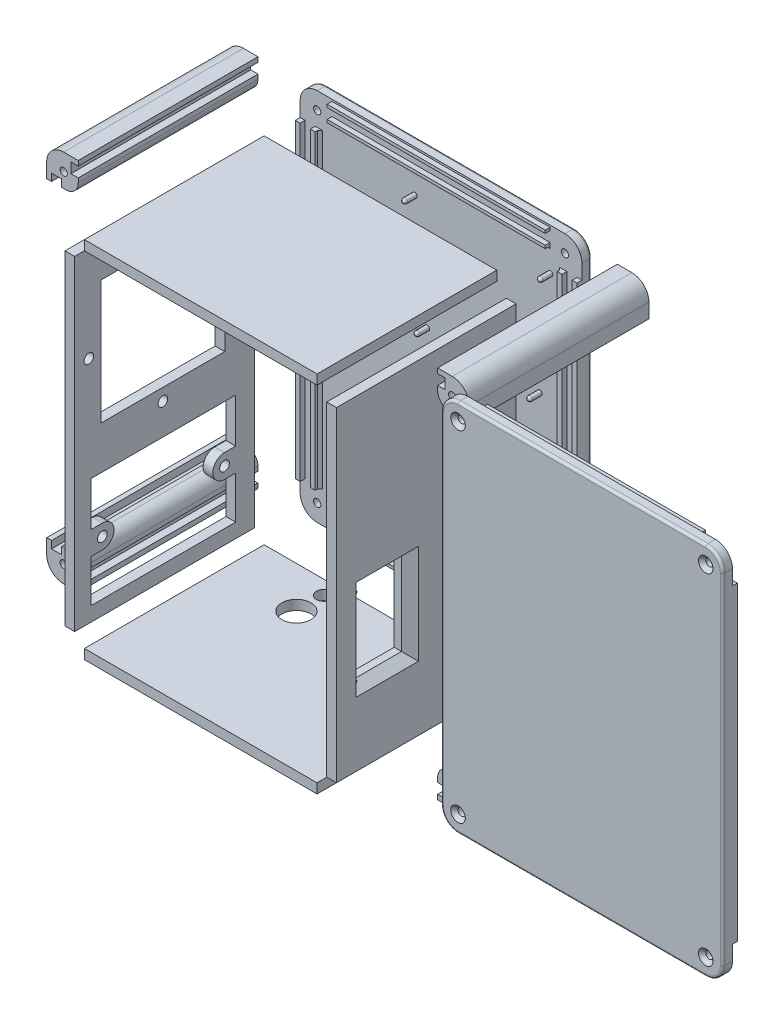
SolidWorks part; units mm, degrees
note: The reader was unsure of these and kept them because the rebuilt part matched: shared geometry of "Эскиз10<3>", "Эскиз10<4>".
other "Розетка"
other "Стойка 4"
other "Стойка 3"
other "Стойка 2"
other "Стойка 1"
other "Левая стенка"
other "Правая стенка"
other "НК"
other "ВК"
ref_plane "Спереди" through (0, 0, 0) normal (0, 0, 1) x (1, 0, 0)
ref_plane "Сверху" through (0, 0, 0) normal (0, 1, 0) x (1, 0, 0)
ref_plane "Справа" through (0, 0, 0) normal (1, 0, 0) x (0, 0, -1)
sketch "Эскиз1" plane through (0, 0, 0) normal (0, 0, 1) x (1, 0, 0)
  line L0 (-59.9, -15.0083) -> (-59.9, -81.9083)
  line L1 (-55.9, 51.8917) -> (-55.9, -81.9083)
  line L2 (-59.9, -81.9083) -> (-55.9, -81.9083)
  line L3 (-60, -82.0083) -> (-60, -79.0083)
  line L4 (-59.9, -15.0083) -> (-59.9, -82.0083) construction
  line L5 (-59.9, 51.8917) -> (-59.9, -81.9083)
  line L7 (-59.9, -15.0083) -> (-59.9, -81.9083)
  line L8 (-55.9, 51.8917) -> (-55.9, -81.9083)
  line L9 (-59.9, -81.9083) -> (-55.9, -81.9083)
  line L10 (-59.9, 51.8917) -> (-59.9, -81.9083)
  line L11 (-55.9, 51.8917) -> (-55.9, -81.9083)
  line L12 (43.9, -85.9083) -> (-51.9, -85.9083)
  line L13 (44, -87.9083) -> (-52, -87.9083) construction
  line L14 (-4, 59.9917) -> (-4, -91.0083) construction
  line L15 (-55, 61.9917) -> (-49, 61.9917)
  line L16 (-54, -79.0083) -> (-55.8, -79.0083)
  line L17 (-61, -79.0083) -> (-62, -79.0083)
  line L18 (-51.9, -89.9083) -> (-51.9, -85.9083)
  line L22 (-55.8, -82.0083) -> (-60, -82.0083)
  line L23 (-55.8, -82.0083) -> (-55.8, -79.0083)
  line L24 (-60, -90.0083) -> (-49, -79.0083) construction
  line L25 (-60, -79.0083) -> (-61, -79.0083)
  line L26 (54, 54.9917) -> (54, 48.9917)
  line L27 (47, 61.9917) -> (41, 61.9917)
  line L28 (48.0607, 56.0524) -> (41, 48.9917) construction
  line L29 (43.9, -89.9083) -> (-51.9, -89.9083)
  line L31 (-49, -90.0083) -> (-49, -92.0083)
  line L32 (-52, -85.8083) -> (-49, -85.8083)
  line L33 (-52, -85.8083) -> (-52, -90.0083)
  line L35 (-49, -84.0083) -> (-49, -85.8083)
  line L36 (-52, -90.0083) -> (-49, -90.0083)
  line L37 (-57.9, -81.9083) -> (-57.9, -82.0083) construction
  line L38 (49.9, 51.9917) -> (49.9, 51.8917) construction
  line L42 (52, -90.0083) -> (41, -79.0083) construction
  line L43 (44, -90.0083) -> (41, -90.0083)
  line L44 (41, -84.0083) -> (41, -85.8083)
  line L46 (44, -85.8083) -> (44, -90.0083)
  line L47 (44, -85.8083) -> (41, -85.8083)
  line L48 (41, -90.0083) -> (41, -92.0083)
  line L49 (52, -79.0083) -> (54, -79.0083)
  line L50 (47.8, -82.0083) -> (47.8, -79.0083)
  line L51 (47.8, -82.0083) -> (52, -82.0083)
  line L53 (43.9, -89.9083) -> (43.9, -85.9083)
  line L54 (46, -79.0083) -> (47.8, -79.0083)
  line L55 (47.9, 51.8917) -> (47.9, -81.9083)
  line L56 (51.9, 51.8917) -> (51.9, -81.9083)
  line L57 (51.9, -81.9083) -> (47.9, -81.9083)
  line L58 (47.9, 51.8917) -> (47.9, -81.9083)
  line L59 (51.9, 51.8917) -> (51.9, -81.9083)
  line L60 (51.9, 51.8917) -> (51.9, -81.9083)
  line L61 (52, -82.0083) -> (52, -79.0083)
  line L62 (51.9, -81.9083) -> (47.9, -81.9083)
  line L63 (47.9, 51.8917) -> (47.9, -81.9083)
  line L64 (51.9, 51.8917) -> (51.9, -81.9083)
  line L65 (52, 59.9917) -> (50.5355, 58.5272) construction
  line L66 (-57.9, 51.8917) -> (-57.9, 51.9917) construction
  line L67 (-60, 59.9917) -> (-49, 48.9917) construction
  line L68 (44, 57.8917) -> (-52, 57.8917) construction
  line L69 (51.9, 51.8917) -> (47.9, 51.8917)
  line L70 (52, 51.9917) -> (52, 48.9917)
  line L71 (51.9, 51.8917) -> (47.9, 51.8917)
  line L72 (46, 48.9917) -> (47.8, 48.9917)
  line L73 (43.9, 59.8917) -> (43.9, 55.8917)
  line L75 (47.8, 51.9917) -> (52, 51.9917)
  line L76 (47.8, 51.9917) -> (47.8, 48.9917)
  line L77 (52, 48.9917) -> (54, 48.9917)
  line L78 (41, 59.9917) -> (41, 61.9917)
  line L79 (44, 55.7917) -> (41, 55.7917)
  line L80 (44, 55.7917) -> (44, 59.9917)
  line L82 (41, 53.9917) -> (41, 55.7917)
  line L83 (44, 59.9917) -> (41, 59.9917)
  line L84 (-52, 59.9917) -> (-49, 59.9917)
  line L85 (-49, 53.9917) -> (-49, 55.7917)
  line L87 (-52, 55.7917) -> (-52, 59.9917)
  line L88 (-52, 55.7917) -> (-49, 55.7917)
  line L89 (-49, 59.9917) -> (-49, 61.9917)
  line L90 (43.9, 59.8917) -> (-51.9, 59.8917)
  line L91 (-60, 48.9917) -> (-62, 48.9917)
  line L92 (-55.8, 51.9917) -> (-55.8, 48.9917)
  line L93 (-55.8, 51.9917) -> (-60, 51.9917)
  line L95 (-51.9, 59.8917) -> (-51.9, 55.8917)
  line L96 (-54, 48.9917) -> (-55.8, 48.9917)
  line L97 (43.9, 55.8917) -> (-51.9, 55.8917)
  line L98 (-59.9, 51.8917) -> (-55.9, 51.8917)
  line L99 (-59.9, -15.0083) -> (-59.9, 51.8917)
  line L100 (-60, 51.9917) -> (-60, 48.9917)
  line L101 (-59.9, 51.8917) -> (-55.9, 51.8917)
  line L102 (-59.9, -15.0083) -> (-59.9, 51.8917)
  line L103 (49.9, -81.9083) -> (49.9, -82.0083) construction
  line L104 (-55.9, -15.0083) -> (47.9, -15.0083) construction
  line L105 (-57.9, -15.0083) -> (-57.9, -82.0083) construction
  line L106 (-62, 54.9917) -> (-62, 48.9917)
  line L107 (44, 59.9917) -> (41, 59.9917)
  line L108 (52, 51.9917) -> (52, 48.9917)
  line L109 (47, -92.0083) -> (41, -92.0083)
  line L110 (54, -85.0083) -> (54, -79.0083)
  line L111 (-62, -85.0083) -> (-62, -79.0083)
  line L112 (-55, -92.0083) -> (-49, -92.0083)
  circle A0 centre (47, -85.0083) radius 1.5
  arc A1 (41, -84.0083) -> (46, -79.0083) centre (46, -84.0083) cw
  circle A3 centre (-55, 54.9917) radius 1.5
  arc A4 (-49, 53.9917) -> (-54, 48.9917) centre (-54, 53.9917) cw
  arc A8 (41, 53.9917) -> (46, 48.9917) centre (46, 53.9917) ccw
  circle A9 centre (47, 54.9917) radius 1.5
  arc A10 (-62, 54.9917) -> (-55, 61.9917) centre (-55, 54.9917) cw
  arc A11 (-49, -84.0083) -> (-54, -79.0083) centre (-54, -84.0083) ccw
  circle A16 centre (-55, -85.0083) radius 1.5
  arc A17 (54, 54.9917) -> (47, 61.9917) centre (47, 54.9917) ccw
  arc A25 (54, -85.0083) -> (47, -92.0083) centre (47, -85.0083) cw
  arc A26 (-62, -85.0083) -> (-55, -92.0083) centre (-55, -85.0083) ccw
  point P3 (-60, 59.9917)
  point P4 (52, 59.9917)
  point P5 (-60, -90.0083)
  point P19 (52, 59.9917)
  point P40 (-4, -87.9083)
  point P82 (-4, -89.9083)
  point P88 (-4, -85.9083)
  point P90 (47.9, -15.0083)
  point P92 (52, -90.0083)
  point P96 (49.9, -15.0083)
  point P119 (51.9, -15.0083)
  point P143 (-55.9, -15.0083)
  point P144 (-4, 55.8917)
  point P145 (-4, 59.8917)
  point P146 (-4, 57.8917)
  point P147 (-60, 59.9917)
  dimension "D3" = 3
  dimension "D2" = 4.2
  dimension "D4" = 2
  dimension "D6" = 0.1
extrude "Бобышка-Вытянуть1" add sketch "Эскиз1" along normal blind 74
ref_plane "Плоскость5" through (0, 0, -0.1) normal (0, 0, -1) x (-1, 0, 0)
sketch "Эскиз3" plane through (0, 0, -0.1) normal (0, 0, -1) x (-1, 0, 0)
  line L13 (4, 60.9917) -> (4, -91.0083) construction
  line L14 (-53, -15.0083) -> (61, -15.0083) construction
  line L15 (-41, 61.9917) -> (-47, 61.9917)
  line L16 (-54, 54.9917) -> (-54, 48.9917)
  line L17 (-54, 48.9917) -> (-54, -79.0083)
  line L18 (-54, -79.0083) -> (-54, -85.0083)
  line L19 (-47, -92.0083) -> (-41, -92.0083)
  line L20 (-41, -92.0083) -> (49, -92.0083)
  line L21 (49, -92.0083) -> (55, -92.0083)
  line L22 (62, -85.0083) -> (62, -79.0083)
  line L23 (62, -79.0083) -> (62, 48.9917)
  line L24 (62, 48.9917) -> (62, 54.9917)
  line L25 (55, 61.9917) -> (49, 61.9917)
  line L26 (49, 61.9917) -> (-41, 61.9917)
  arc A5 (-47, 61.9917) -> (-54, 54.9917) centre (-47, 54.9917) ccw
  arc A6 (-54, -85.0083) -> (-47, -92.0083) centre (-47, -85.0083) ccw
  arc A7 (55, -92.0083) -> (62, -85.0083) centre (55, -85.0083) ccw construction
  arc A8 (55, -92.0083) -> (62, -85.0083) centre (55, -85.0083) ccw
  arc A9 (62, 54.9917) -> (55, 61.9917) centre (55, 54.9917) ccw construction
  arc A10 (62, 54.9917) -> (55, 61.9917) centre (55, 54.9917) ccw
  point P41 (-47, 54.9917)
extrude "Бобышка-Вытянуть3" add sketch "Эскиз3" along normal blind 4 separate body
sketch "Эскиз4" plane through (0, 0, -0.1) normal (0, 0, 1) x (1, 0, 0)
  line L0 (-4, 61.2063) -> (-4, -91.0083) construction
  line L2 (-62, -85.0083) -> (-62, 54.9917) construction
  line L3 (-62, -15.0083) -> (54, -15.0083) construction
  line L6 (-60, 48.8917) -> (-60, -78.9083)
  line L7 (-62, 48.8917) -> (-62, -78.9083)
  line L8 (-62, 48.8917) -> (-60, 48.8917)
  line L9 (-60, 48.9917) -> (-62, 48.9917) construction
  line L10 (47.8, 48.8917) -> (47.8, -78.9083)
  line L11 (-48.9, 59.9917) -> (40.9, 59.9917)
  line L12 (-48.9, 61.2063) -> (-48.9, 59.9917)
  line L13 (-48.9, 61.2063) -> (40.9, 61.2063)
  line L14 (40.9, 61.2063) -> (40.9, 59.9917)
  line L15 (54, 48.8917) -> (52, 48.8917)
  line L16 (54, 48.8917) -> (54, -78.9083)
  line L17 (52, 48.8917) -> (52, -78.9083)
  line L18 (45.8, 48.8917) -> (45.8, -78.9083)
  line L19 (54, -78.9083) -> (52, -78.9083)
  line L20 (40.9, -91.2229) -> (40.9, -90.0083)
  line L21 (-48.9, -91.2229) -> (40.9, -91.2229)
  line L22 (-48.9, -91.2229) -> (-48.9, -90.0083)
  line L23 (-48.9, -90.0083) -> (40.9, -90.0083)
  line L24 (-62, -78.9083) -> (-60, -78.9083)
  line L25 (-57.9, 51.9917) -> (-57.9, -82.0083) construction
  line L26 (-55.8, 51.9917) -> (-60, 51.9917) construction
  line L27 (-55.8, -82.0083) -> (-60, -82.0083) construction
  line L28 (-53.8, -78.9083) -> (-55.8, -78.9083)
  line L29 (-53.8, 48.8917) -> (-55.8, 48.8917)
  line L30 (-53.8, 48.8917) -> (-53.8, -78.9083)
  line L31 (-55.8, 48.8917) -> (-55.8, -78.9083)
  line L32 (45.8, 48.8917) -> (47.8, 48.8917)
  line L33 (45.8, -78.9083) -> (47.8, -78.9083)
  line L34 (-51.9, 57.8917) -> (44, 57.8917) construction
  line L35 (-51.9, 59.8917) -> (-51.9, 55.8917) construction
  line L36 (44, 55.7917) -> (44, 59.9917) construction
  line L37 (40.9, 54.5771) -> (40.9, 55.7917)
  line L38 (-48.9, 54.5771) -> (40.9, 54.5771)
  line L39 (-48.9, 54.5771) -> (-48.9, 55.7917)
  line L40 (-48.9, 55.7917) -> (40.9, 55.7917)
  line L41 (-48.9, -85.8083) -> (40.9, -85.8083)
  line L42 (-48.9, -84.5937) -> (-48.9, -85.8083)
  line L43 (-48.9, -84.5937) -> (40.9, -84.5937)
  line L44 (40.9, -84.5937) -> (40.9, -85.8083)
  point P2 (0, 0)
  point P3 (0, 0)
  point P8 (0, 0)
  point P13 (-4, -90.0083)
  point P21 (0, 0)
  point P22 (47.8, -15.0083)
  point P28 (-4, 59.9917)
  point P34 (52, -15.0083)
  point P41 (-60, -15.0083)
  point P48 (-55.8, -15.0083)
  point P61 (-4, 55.7917)
  point P66 (-4, -85.8083)
  dimension "D1" = 0.1
extrude "Бобышка-Вытянуть4" add sketch "Эскиз4" along normal blind 2
sketch "Эскиз5" plane through (0, 0, -4.1) normal (0, 0, -1) x (-1, 0, 0)
  line L0 (4, 60.9917) -> (4, -91.0083) construction
  line L3 (-53, -15.0083) -> (61, -15.0083) construction
  circle A0 centre (-47, 54.9917) radius 1.5
  circle A1 centre (55, 54.9917) radius 1.5
  circle A2 centre (55, -85.0083) radius 1.5
  circle A3 centre (-47, -85.0083) radius 1.5
  point P2 (0, 0)
  point P8 (0, 0)
  point P9 (0, 0)
  point P21 (0, 0)
  point P22 (0, 0)
  point P23 (0, 0)
  point P24 (0, 0)
  point P25 (0, 0)
extrude "Вырез-Вытянуть1" cut sketch "Эскиз5" against normal through all
move or copy body "Тело-Переместить/Копировать1" bodies to move or copy 119 copy yes number of copies 1 translate (140, 0, 80) parameters "D1"=140, "D2"=0, "D3"=80
move or copy body "Тело-Переместить/Копировать2" bodies to move or copy 122 copy no rotation origin (0, -15.0083, 78.9) rotation axis (1, 0, 0) rotation angle 180
sketch "Эскиз7" plane through (0, 0, -0.1) normal (0, 0, 1) x (1, 0, 0)
  line L0 (-11.5142, 1.9824) -> (38.4858, 1.9824) construction
  line L1 (38.4858, 1.9824) -> (38.4858, -18.0176) construction
  line L2 (38.4858, -18.0176) -> (-11.5142, -18.0176) construction
  line L3 (-11.5142, -18.0176) -> (-11.5142, 1.9824) construction
  circle A0 centre (-9.7042, 0.0824) radius 1
  circle A1 centre (36.6758, 0.0824) radius 1
  circle A2 centre (-9.7042, -16.1176) radius 1
  circle A3 centre (36.6758, -16.1176) radius 1
  circle A4 centre (42.4618, -70.067) radius 1.5
  circle A5 centre (-9.8382, -75.167) radius 1.5
  circle A6 centre (-8.8882, -26.767) radius 1.5
  circle A7 centre (42.4618, -42.067) radius 1.5
  circle A8 centre (41.0606, 44.8177) radius 1
  circle A9 centre (41.0606, 18.9377) radius 1
  circle A10 centre (-14.8194, 44.8177) radius 1
  circle A11 centre (-14.8194, 18.9377) radius 1
extrude "Бобышка-Вытянуть5" add sketch "Эскиз7" along normal blind 5
sketch "Эскиз8" plane through (-55.9, 0, 0) normal (1, 0, 0) x (0, 0, -1)
  line L0 (-37.4426, -30.6934) -> (-37.4426, -76.0083) construction
  line L1 (-17.0925, -53.7186) -> (-57.7928, -53.7186) construction
  line L2 (-74, -79.0083) -> (0, -79.0083) construction
  line L3 (-74, 48.9917) -> (0, 48.9917) construction
  line L4 (-2.4, 46.9917) -> (-2.4, -24.0083) construction
  line L5 (-2.4, -24.0083) -> (-73.1772, -24.0083) construction
  line L6 (-73.1772, -24.0083) -> (-73.1772, 46.9917) construction
  line L7 (-73.1772, 46.9917) -> (-2.4, 46.9917) construction
  line L8 (-2.4, 46.9917) -> (-73.1772, -24.0083) construction
  line L9 (-2.4, -24.0083) -> (-73.1772, 46.9917) construction
  line L10 (-68.1772, -17.9534) -> (-68.1772, 43.0466) construction
  line L11 (-68.1772, 43.0466) -> (-7.1772, 43.0466) construction
  line L12 (-7.1772, 43.0466) -> (-7.1772, -17.9534) construction
  line L13 (-7.1772, -17.9534) -> (-68.1772, -17.9534) construction
  line L14 (-12.1772, -12.9534) -> (-63.1772, -12.9534)
  line L15 (-63.1772, -12.9534) -> (-63.1772, 38.0466)
  line L16 (-63.1772, 38.0466) -> (-12.1772, 38.0466)
  line L17 (-12.1772, 38.0466) -> (-12.1772, -12.9534)
  line L18 (-37.6772, 12.5466) -> (-37.6772, -22.9534) construction
  line L19 (-37.6772, 12.5466) -> (-37.6772, 48.0466) construction
  line L20 (-37.6772, 12.5466) -> (-2.1772, 12.5466) construction
  line L21 (-37.6772, 12.5466) -> (-73.1772, 12.5466) construction
  line L22 (-7.6926, -30.6934) -> (-7.6926, -48.8937)
  line L23 (-7.6926, -48.8937) -> (-12.3438, -48.8937)
  line L24 (-12.2934, -58.4934) -> (-7.6926, -58.4934)
  line L25 (-7.6926, -58.4934) -> (-7.6926, -76.0083)
  line L26 (-7.6926, -76.0083) -> (-67.1926, -76.0083)
  line L27 (-67.1926, -76.0083) -> (-67.1926, -58.4933)
  line L28 (-67.1926, -58.4933) -> (-62.6007, -58.4933)
  line L29 (-62.5503, -48.8937) -> (-67.1926, -48.8937)
  line L30 (-67.1926, -48.8937) -> (-67.1926, -30.6934)
  line L31 (-67.1926, -30.6934) -> (-7.6926, -30.6934)
  line L32 (-1.9, -78.9083) -> (-1.9, 48.8917) construction
  circle A0 centre (-37.6772, 43.0466) radius 2
  circle A1 centre (-7.1772, 12.5466) radius 2
  circle A2 centre (-37.6772, -17.9534) radius 2
  circle A3 centre (-68.1772, 12.5466) radius 2
  circle A4 centre (-62.5926, -53.6934) radius 2
  circle A5 centre (-12.2926, -53.6934) radius 2
  arc A6 (-12.3438, -48.8937) -> (-12.2934, -58.4934) centre (-12.2926, -53.6934) ccw
  arc A7 (-62.6007, -58.4933) -> (-62.5503, -48.8937) centre (-62.5926, -53.6934) ccw
  dimension "D1" = 3
  dimension "D2" = 2
  dimension "D3" = 0.5
extrude "Вырез-Вытянуть2" cut sketch "Эскиз8" against normal through all
sketch "Эскиз9" plane through (0, -85.9083, 0) normal (0, 1, 0) x (1, 0, 0)
  line L0 (-21.5383, -17.0591) -> (-21.5383, 5.4723) construction
  circle A0 centre (-21.5383, -5.7934) radius 3
  circle A1 centre (-21.5383, -17.0591) radius 6
extrude "Вырез-Вытянуть3" cut sketch "Эскиз9" against normal blind 5
sketch "Эскиз10" plane through (47.9, 0, 0) normal (-1, 0, 0) x (0, 0, 1)
  line L0 (43.2359, -52.4668) -> (62.9059, -52.4668)
  line L1 (62.9059, -52.4668) -> (62.9059, -17.4668)
  line L2 (62.9059, -17.4668) -> (42.8359, -17.4668)
  line L3 (39.9059, -17.4668) -> (39.9059, -52.4668) construction
  line L5 (62.9059, -52.4668) -> (39.9059, -17.4668) construction
  line L6 (62.9059, -17.4668) -> (39.9059, -52.4668) construction
  line L7 (15.3005, -42.6198) -> (15.3005, -27.6198)
  line L8 (15.3005, -27.6198) -> (12.0005, -27.6198)
  line L9 (12.0005, -27.6198) -> (12.0005, -42.6198)
  line L10 (12.0005, -42.6198) -> (15.3005, -42.6198)
  line L11 (15.3005, -42.6198) -> (12.0005, -27.6198) construction
  line L12 (15.3005, -27.6198) -> (12.0005, -42.6198) construction
  line L13 (43.2359, -17.4668) -> (43.2359, -52.4668)
  line L14 (62.9059, -52.4668) -> (62.9059, -17.4668)
  line L15 (62.9059, -17.4668) -> (43.2359, -17.4668)
  line L16 (43.2359, -17.4668) -> (43.2359, -52.4668)
  line L17 (43.2359, -52.4668) -> (62.9059, -52.4668)
  line L18 (63.3059, -52.8668) -> (63.3059, -17.0668)
  line L19 (63.3059, -17.0668) -> (42.8359, -17.0668)
  line L20 (42.8359, -17.0668) -> (42.8359, -52.8668)
  line L21 (42.8359, -52.8668) -> (63.3059, -52.8668)
  line L22 (64.3059, -53.8668) -> (64.3059, -16.0668)
  line L23 (64.3059, -16.0668) -> (41.8359, -16.0668)
  line L24 (41.8359, -16.0668) -> (41.8359, -53.8668)
  line L25 (41.8359, -53.8668) -> (64.3059, -53.8668)
  circle A2 centre (65.6059, -18.9868) radius 1
  circle A3 centre (65.6059, -50.9468) radius 1
  circle A4 centre (37.2059, -18.9868) radius 1
  circle A5 centre (37.2059, -50.9468) radius 1
  circle A6 centre (65.6059, -18.9868) radius 2.65
  circle A7 centre (65.6059, -50.9468) radius 2.65
  circle A8 centre (37.2059, -18.9868) radius 2.65
  circle A9 centre (37.2059, -50.9468) radius 2.65
extrude "Вырез-Вытянуть4" cut sketch "Эскиз10" against normal blind 5 contours L9 L10 L7 L8 | L2 L13 L0 L1
extrude "Вырез-Вытянуть5" cut sketch "Эскиз10<3>" against normal blind 3 contours A4 | A2 | A3 | A5
sketch "Эскиз10<3>" plane through (47.9, 0, 0) normal (-1, 0, 0) x (0, 0, 1) same geometry as "Эскиз10"
extrude "Бобышка-Вытянуть6" add sketch "Эскиз10<4>" along normal blind 3 contours A8 A4 | A9 A5 | L22 A7 A3 | L22 A6 A2 | L22 A6 L18 | L22 A7 L18 | L2 L13 L0 L1
sketch "Эскиз10<4>" plane through (47.9, 0, 0) normal (-1, 0, 0) x (0, 0, 1) same geometry as "Эскиз10"
chamfer "Фаска1" distance 3 distance2 4 4 edges at (51.9, -34.9668, 43.2359) (51.9, -52.4668, 53.0709) (51.9, -34.9668, 62.9059) (51.9, -17.4668, 53.0709)
fillet "Скругление1" radius 1 8 edges at (191.9497, 59.9414, 81.9) (136, 61.9917, 81.9) (80.0503, 59.9414, 81.9) (78, -15.0083, 81.9) (191.9497, -89.9581, 81.9) (80.0503, -89.9581, 81.9) (136, -92.0083, 81.9) (194, -15.0083, 81.9)
fillet "Скругление2" radius 1 8 edges at (-59.9497, 59.9414, -4.1) (-62, -15.0083, -4.1) (-59.9497, -89.9581, -4.1) (-4, -92.0083, -4.1) (51.9497, -89.9581, -4.1) (54, -15.0083, -4.1) (51.9497, 59.9414, -4.1) (-4, 61.9917, -4.1)
chamfer "Фаска4" distance 1 angle 45 4 edges at (-4, -84.5937, -0.1) (45.8, -15.0083, -0.1) (-53.8, -15.0083, -0.1) (-4, 54.5771, -0.1)
chamfer "Фаска2" distance 1.5 angle 45 4 edges at (45.5, 54.9917, -4.1) (48.5, -85.0083, -4.1) (-56.5, -85.0083, -4.1) (-53.5, 54.9917, -4.1)
chamfer "Фаска3" distance 1.5 angle 45 4 edges at (188.5, 54.9917, 81.9) (83.5, 54.9917, 81.9) (86.5, -85.0083, 81.9) (185.5, -85.0083, 81.9)
fillet "Скругление3" radius 1 12 edges at (43.9618, -70.067, 4.9) (-8.3382, -75.167, 4.9) (-7.3882, -26.767, 4.9) (43.9618, -42.067, 4.9) (37.6758, -16.1176, 4.9) (-8.7042, -16.1176, 4.9) (-8.7042, 0.0824, 4.9) (37.6758, 0.0824, 4.9) (42.0606, 18.9377, 4.9) (42.0606, 44.8177, 4.9) (-13.8194, 18.9377, 4.9) (-13.8194, 44.8177, 4.9)
move or copy body "Тело-Переместить/Копировать9" bodies to move or copy 103 102 copy no translate (-30.2697, 0, 0) parameters "D1"=30.2697, "D2"=0, "D3"=0
move or copy body "Тело-Переместить/Копировать10" bodies to move or copy 105 104 copy no translate (27.7083, 0, 0) parameters "D1"=27.7083, "D2"=0, "D3"=0
move or copy body "Тело-Переместить/Копировать11" bodies to move or copy 121 108 127 124 copy no translate (0, 0, 24.8527) parameters "D1"=0, "D2"=0, "D3"=24.8527
